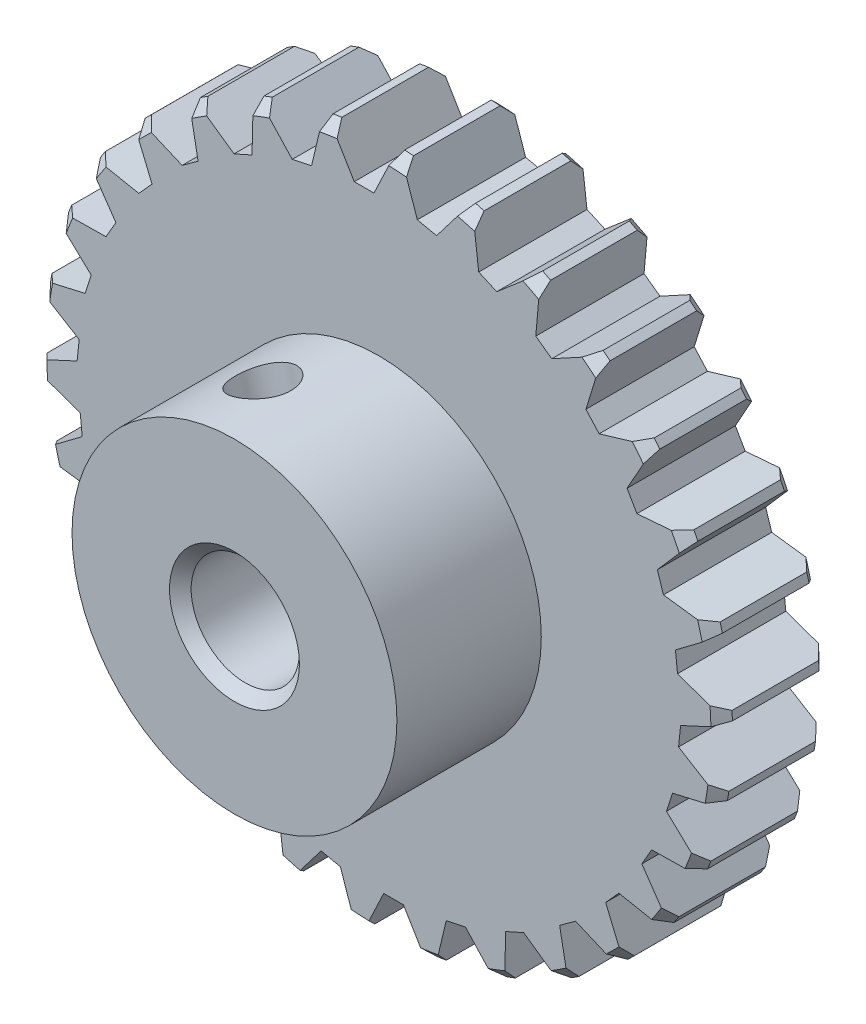
SolidWorks part; units mm, degrees
ref_plane "前视基准面" through (0, 0, 0) normal (0, 0, 1) x (1, 0, 0)
ref_plane "上视基准面" through (0, 0, 0) normal (0, 1, 0) x (1, 0, 0)
ref_plane "右视基准面" through (0, 0, 0) normal (1, 0, 0) x (0, 0, -1)
sketch "草图1" plane through (0, 0, 0) normal (0, 0, 1) x (1, 0, 0)
  circle A0 centre (0, 0) radius 9.5
  circle A1 centre (0, 0) radius 1.5
  dimension "D1" = 19
  dimension "D2" = 3
extrude "凸台-拉伸1" add sketch "草图1" along normal blind 3
sketch "草图2" plane through (0, 0, 3) normal (0, 0, 1) x (1, 0, 0)
  circle A0 centre (0, 0) radius 1.5 construction
  circle A1 centre (0, 0) radius 1.5
  circle A2 centre (0, 0) radius 4.5
  dimension "D1" = 9
extrude "凸台-拉伸2" add sketch "草图2" along normal blind 4
chamfer "倒角1" distance 0.3 angle 45 2 edges at (9.5, 0, 0) (9.5, 0, 3)
hole_wizard "M2 螺纹孔1" positions "3D草图1" profile "草图3" tap size "M2" standard "GB"
sketch3d "3D草图1"
  point P0 (-1.1875, 4.3405, 5.0357)
sketch "草图3" plane through (-1.1875, 4.3405, 5.0357) normal (0, 0, 1) x (-0.9646, -0.2639, 0)
  line L0 (0, 0) -> (0, 4.4807)
  line L1 (0, 4.4807) -> (0.8, 4)
  line L2 (0.8, 4) -> (0.8, 0)
  line L5 (0.8, 0) -> (0, 0)
  line L10 (0, 4.4807) -> (-0.8, 4) construction
  line L11 (0, -6.35) -> (0, 107.95) construction
  dimension "螺纹孔钻头直径" = 1.6
  dimension "螺纹孔钻头深度" = 4
  dimension "导头角度" = 118
cosmetic thread "孔螺蚊线1" parameters "D1"=3, "D2"=2
sketch "草图4" plane through (0, 0, 0) normal (0, 0, -1) x (-1, 0, 0)
  line L0 (0, 0) -> (1.4928, 9.6878) construction
  line L1 (0, 0) -> (0.6941, 14.399) construction
  line L2 (-0.5072, 9.6878) -> (1.4928, 9.6878)
  line L3 (1.4928, 9.6878) -> (0.6821, 8.3336)
  line L4 (0.6821, 8.3336) -> (0.1355, 8.3336)
  line L5 (0.1355, 8.3336) -> (-0.5072, 9.6878)
  dimension "D1" = 6
  dimension "D2" = 2
  dimension "D3" = 1.3542
  dimension "D4" = 0.5466
extrude "切除-拉伸1" cut sketch "草图4" against normal through all
ref_axis "基准轴1" through (0, 0, 0) along (0, 0, -1)
pattern_circular "阵列(圆周)1" count 30 every 12 about axis through (0, 0, 0) along (0, 0, -1) of "切除-拉伸1"
chamfer "倒角2" distance 0.3 angle 45 1 edges at (1.5, 0, 7)
